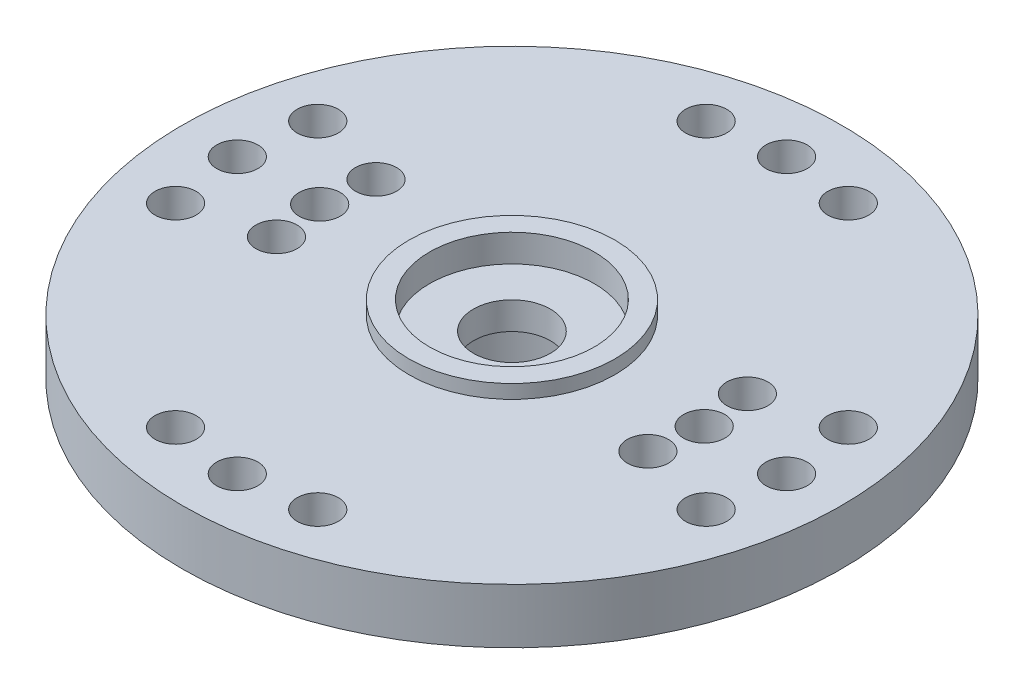
SolidWorks part; units mm, degrees
material "PC High Viscosity"
ref_plane "Front Plane" through (0, 0, 0) normal (0, 0, 1) x (1, 0, 0)
ref_plane "Top Plane" through (0, 0, 0) normal (0, 1, 0) x (1, 0, 0)
ref_plane "Right Plane" through (0, 0, 0) normal (1, 0, 0) x (0, 0, -1)
sketch "Sketch1" plane through (0, 0, 0) normal (0, 0, 1) x (1, 0, 0)
  line L0 (0, 0) -> (0, -4.5) construction
  line L1 (0, -55) -> (0, 55) construction
  line L2 (55, 0) -> (-55, 0) construction
  line L3 (-12, 0) -> (-3.75, 0)
  line L4 (-12, 0) -> (-12, -2)
  line L5 (-12, -2) -> (-4.45, -2)
  line L6 (-1.4, 0.5) -> (-1.4, -4.5)
  line L8 (-4.45, -2) -> (-4.45, -4.5)
  line L9 (-4.45, -4.5) -> (-1.4, -4.5)
  line L10 (-3.75, 0.5) -> (-1.4, 0.5)
  line L11 (-3.75, 0.5) -> (-3.75, 0)
  dimension "D1" = 8.9
  dimension "D2" = 2.5
  dimension "D3" = 4.5
  dimension "D4" = 24
  dimension "D5" = 2.8
  dimension "D6" = 7.5
  dimension "D7" = 5
revolve "Revolve1" add sketch "Sketch1" angle 360 about L0
hole_wizard "Ø1.5 (1.5) Diameter Hole1" positions "Sketch3" profile "Sketch2" hole size "Ø1.5" standard "Ansi Metric" end condition up to next
sketch "Sketch3" plane through (0, 0, 0) normal (0, 1, 0) x (-1, 0, 0)
  line L5 (0, 0) -> (-2.5882, -9.6593) construction
  line L6 (0, 0) -> (2.5882, -9.6593) construction
  line L8 (0, 0) -> (0, -10) construction
  circle A0 centre (0, 0) radius 10 construction
  point P0 (0, -10)
  point P23 (2.5882, -9.6593)
  point P25 (-2.5882, -9.6593)
  dimension "D1" = 20
  dimension "D2" = 15
  dimension "D3" = 15
sketch "Sketch2" plane through (0, 0, -10) normal (1, 0, 0) x (0, 0, 1)
  line L0 (0, 0) -> (0, 2)
  line L1 (0, 2) -> (0.75, 2)
  line L2 (0.75, 2) -> (0.75, 0)
  line L5 (0.75, 0) -> (0, 0)
  line L11 (0, -6.35) -> (0, 107.95) construction
  dimension "Thru Hole Dia." = 1.5
  dimension "Thru Hole Depth" = 2
pattern_circular "CirPattern1" count 4 over 360 about axis through (0, 0, 0) along (0, -1, 0) of "Ø1.5 (1.5) Diameter Hole1"
sketch "Sketch4" plane through (0, 0.5, 0) normal (0, 1, 0) x (-1, 0, 0)
  circle A0 centre (0, 0) radius 3
  dimension "D1" = 6
extrude "Cut-Extrude1" cut sketch "Sketch4" against normal blind 1
sketch "Sketch5" plane through (0, -4.5, 0) normal (0, -1, 0) x (1, 0, 0)
  circle A0 centre (0, 0) radius 3
  dimension "D1" = 6
extrude "Cut-Extrude2" cut sketch "Sketch5" against normal blind 3
hole_wizard "Ø1.5 (1.5) Diameter Hole2" positions "Sketch7" profile "Sketch6" hole size "Ø1.5" standard "Ansi Metric" end condition up to next
sketch "Sketch7" plane through (0, 0, 0) normal (0, 1, 0) x (-1, 0, 0)
  line L0 (7, 0) -> (0, 0) construction
  line L1 (0, 0) -> (6.7615, 1.8117) construction
  line L2 (0, 0) -> (6.7615, -1.8117) construction
  circle A0 centre (0, 0) radius 7 construction
  point P0 (6.7615, -1.8117)
  point P1 (7, 0)
  point P3 (6.7615, 1.8117)
  dimension "D3" = 14
  dimension "D1" = 15
  dimension "D2" = 15
sketch "Sketch6" plane through (-6.7615, 0, -1.8117) normal (1, 0, 0) x (0, 0, 1)
  line L0 (0, 0) -> (0, 2)
  line L1 (0, 2) -> (0.75, 2)
  line L2 (0.75, 2) -> (0.75, 0)
  line L5 (0.75, 0) -> (0, 0)
  line L11 (0, -6.35) -> (0, 107.95) construction
  dimension "Thru Hole Dia." = 1.5
  dimension "Thru Hole Depth" = 2
pattern_circular "CirPattern2" count 2 over 360 about axis through (0, -0.5, 0) along (0, 1, 0) of "Ø1.5 (1.5) Diameter Hole2"
